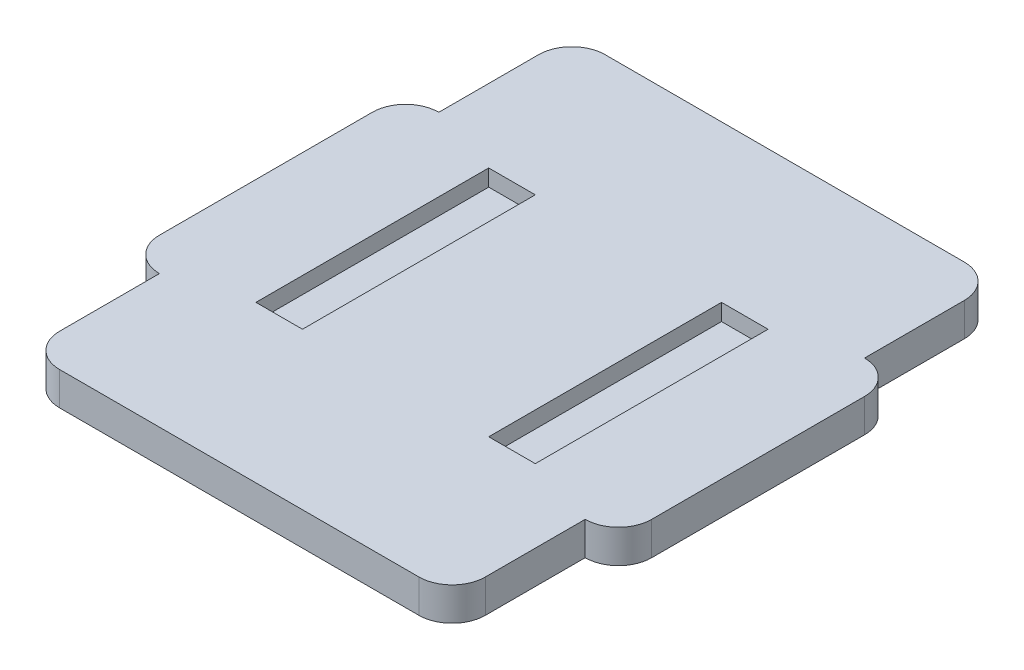
SolidWorks part; units mm, degrees
ref_plane "Front Plane" through (0, 0, 0) normal (0, 0, 1) x (1, 0, 0)
ref_plane "Top Plane" through (0, 0, 0) normal (0, 1, 0) x (1, 0, 0)
ref_plane "Right Plane" through (0, 0, 0) normal (1, 0, 0) x (0, 0, -1)
sketch "Sketch2" plane through (0, 0, 0) normal (0, 1, 0) x (1, 0, 0)
  line L0 (28, 21) -> (35, 21) construction
  line L1 (0, 0) -> (28, 0)
  line L2 (0, 0) -> (0, 42)
  line L3 (0, 42) -> (28, 42)
  line L4 (28, 0) -> (28, 42)
  line L5 (28, 42) -> (35, 42)
  line L6 (28, 42) -> (28, 0)
  line L7 (28, 0) -> (35, 0)
  line L8 (35, 42) -> (35, 0)
  line L9 (28, 38.5) -> (35, 38.5)
  line L10 (31.5, 38.5) -> (31.5, 3.5) construction
  line L11 (28, 3.5) -> (35, 3.5)
  line L12 (26, 0) -> (26, 42)
  line L13 (28, 42) -> (35, 42)
  line L14 (35, 42) -> (37, 42)
  line L15 (35, 42) -> (35, 0)
  line L16 (35, 0) -> (37, 0)
  line L17 (37, 42) -> (37, 0)
  line L18 (37, 42) -> (46, 42)
  line L19 (37, 42) -> (46, 42)
  line L22 (51, 37) -> (51, 5)
  line L23 (2, 42) -> (2, 0)
  line L24 (0, 38.5) -> (-7, 38.5)
  line L25 (0, 3.5) -> (-7, 3.5)
  line L26 (-7, 38.5) -> (-7, 3.5)
  line L27 (0, 42) -> (-7, 42)
  line L28 (-7, 42) -> (-7, 38.5)
  line L29 (0, 0) -> (-7, 0)
  line L30 (-7, 0) -> (-7, 3.5)
  line L31 (-7, 42) -> (-9, 42)
  line L32 (-9, 42) -> (-9, 0)
  line L33 (-9, 0) -> (-7, 0)
  line L34 (-9, 0) -> (-18, 0)
  line L35 (-23, 5) -> (-23, 37)
  line L36 (-18, 42) -> (-9, 42)
  line L37 (37, 0) -> (46, 0)
  line L39 (-18, 0) -> (46, 0)
  line L40 (-18, 0) -> (-18, -15)
  line L41 (-13, -20) -> (41, -20)
  line L42 (46, 0) -> (46, -15)
  line L43 (-18, 42) -> (46, 42)
  line L44 (-18, 42) -> (-18, 57)
  line L45 (-13, 62) -> (41, 62)
  line L46 (46, 42) -> (46, 57)
  arc A0 (51, 37) -> (46, 42) centre (46, 37) ccw
  arc A2 (-18, 0) -> (-23, 5) centre (-18, 5) cw
  arc A3 (-23, 37) -> (-18, 42) centre (-18, 37) cw
  arc A4 (46, 0) -> (51, 5) centre (46, 5) ccw
  arc A5 (-13, -20) -> (-18, -15) centre (-13, -15) cw
  arc A6 (41, -20) -> (46, -15) centre (41, -15) ccw
  arc A7 (46, 57) -> (41, 62) centre (41, 57) ccw
  arc A8 (-13, 62) -> (-18, 57) centre (-13, 57) ccw
  point P49 (0, 0)
  point P50 (0, 0)
  point P51 (0, 0)
  point P56 (46, -20)
  point P61 (-18, 62)
  dimension "D9" = 5
  dimension "D10" = 5
  dimension "D18" = 5
  dimension "D19" = 5
  dimension "D1" = 28
  dimension "D2" = 42
  dimension "D3" = 7
  dimension "D4" = 3.5
  dimension "D5" = 3.5
  dimension "D6" = 2
  dimension "D7" = 2
  dimension "D8" = 3.5
  dimension "D11" = 14
  dimension "D12" = 20
  dimension "D13" = 20
  dimension "D14" = 2
  dimension "D15" = 7
  dimension "D16" = 2
  dimension "D17" = 14
extrude "Boss-Extrude1" add sketch "Sketch2" along normal blind 5 contours L3 L23 L1 L12 | L12 L1 L4 L6 L3 | L11 L4 L7 L8 | L22 A0 L18 L17 | L17 L14 L8 L16 | L6 L9 L8 L5 | A3 L35 A2 L34 L32 L36 | L30 L29 L2 L25 | L32 L33 L30 L26 L28 L31 | L23 L3 L2 L1 | L27 L28 L24 L2 | L41 A6 L42 L37 L16 L7 L1 L29 L33 L34 L40 A5 | L45 A8 L44 L36 L31 L27 L3 L5 L14 L18 L46 A7 region at (1, 0, -21) region at (-3.5, 0, -1.75) region at (14, 0, 9.9249) region at (14, 0, -21) region at (-8, 0, -21) region at (27, 0, -21) region at (14, 0, -51.9249) region at (-3.5, 0, -40.25) region at (-15.8906, 0, -21) region at (31.5, 0, -1.75) region at (36, 0, -21) region at (31.5, 0, -40.25) region at (43.8906, 0, -21)
extrude "Boss-Extrude2" add sketch "Sketch2<3>" along normal blind 2.5 contours L24 L26 L25 L2 | L6 L11 L8 L9 region at (-3.5, 0, -21) region at (31.5, 0, -21)
sketch "Sketch2<3>" plane through (0, 0, 0) normal (0, 1, 0) x (1, 0, 0) same geometry as "Sketch2"
